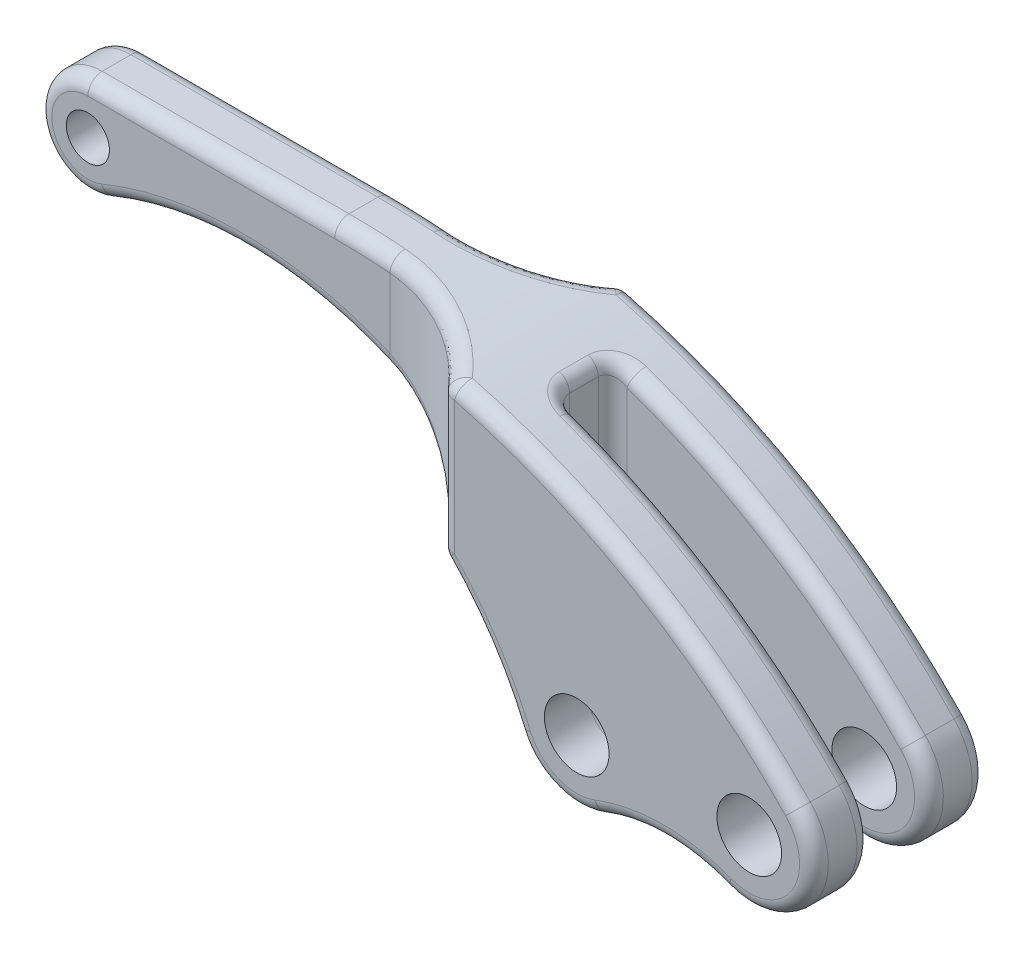
SolidWorks part; units mm, degrees
ref_plane "Front Plane" through (0, 0, 0) normal (0, 0, 1) x (1, 0, 0)
ref_plane "Top Plane" through (0, 0, 0) normal (0, 1, 0) x (1, 0, 0)
ref_plane "Right Plane" through (0, 0, 0) normal (1, 0, 0) x (0, 0, -1)
sketch "Sketch1" plane through (0, 0, 0) normal (0, 0, 1) x (1, 0, 0)
  line L0 (76, -30) -> (100, -30) construction
  line L1 (0, 7) -> (34.3342, 7)
  circle A0 centre (0, 0) radius 3
  arc A1 (0, 7) -> (2.6487, -6.4796) centre (0, 0) ccw
  arc A2 (96.7273, -38.3839) -> (106.4944, -23.7692) centre (100, -30) ccw
  arc A3 (67.6968, -33.4722) -> (79.2727, -38.3839) centre (76, -30) ccw
  arc A4 (79.2727, -38.3839) -> (96.7273, -38.3839) centre (88, -60.7409) cw
  arc A5 (2.6487, -6.4796) -> (67.6968, -33.4722) centre (21.5676, -52.7621) cw
  arc A6 (34.3342, 7) -> (106.4944, -23.7692) centre (34.3342, -93) cw
  circle A7 centre (76, -30) radius 4.5
  circle A8 centre (100, -30) radius 4.5
  dimension "D1" = 6
  dimension "D2" = 14
  dimension "D3" = 18
  dimension "D6" = 18
  dimension "D8" = 24
  dimension "D9" = 50
  dimension "D10" = 100
  dimension "D11" = 9
  dimension "D12" = 9
  dimension "D4" = 100
  dimension "D5" = 30
  dimension "D7" = 24
extrude "Boss-Extrude1" add sketch "Sketch1" along normal mid plane 24
sketch "Sketch2" plane through (0, 0, 0) normal (0, 1, 0) x (1, 0, 0)
  line L0 (-7, 4) -> (-7, -4)
  line L1 (-7, 12) -> (-7, -12) construction
  line L2 (-7, 0) -> (108.7222, 0) construction
  line L3 (-7, -12) -> (58, -12)
  line L4 (-7, -12) -> (2.6487, -12) construction
  line L5 (34.3342, -12) -> (106.4944, -12) construction
  line L6 (-7, -4) -> (42, -4)
  line L7 (-7, -4) -> (-7, -12)
  line L8 (-7, 12) -> (58, 12)
  line L9 (-7, 4) -> (-7, 12)
  line L10 (-7, 4) -> (42, 4)
  line L11 (65, -12) -> (100, -12)
  line L12 (109, 4) -> (65, 4)
  line L13 (109, -12) -> (109, 12) construction
  line L14 (65, 4) -> (65, -4)
  line L15 (65, -4) -> (109, -4)
  line L16 (109, -4) -> (109, 4)
  line L17 (65, -12) -> (65, 17.4758) construction
  arc A0 (42, -4) -> (58, -12) centre (42, -24) cw
  arc A1 (42, 4) -> (58, 12) centre (42, 24) ccw
  point P7 (-7, 0)
  dimension "D3" = 20
  dimension "D1" = 8
  dimension "D2" = 65
  dimension "D4" = 100
  dimension "D5" = 8
  dimension "D6" = 35
extrude "Cut-Extrude1" cut sketch "Sketch2" against normal mid plane 91 contours L10 A1 L8 L9 | A0 L6 L7 L3 | L12 L14 L15 L16
fillet "Fillet3" radius 2 40 edges at (72.4846, -38.2851, 12) (84.2407, -6.3435, 12) (107.4828, -35.0008, 12) (88, -36.7409, 12) (72.4846, -38.2851, -12) (84.2407, -6.3435, -12) (107.4828, -35.0008, -12) (88, -36.7409, -12) (53.068, 5.2295, 7.3417) (49.0899, -11.0186, 5.2988) (53.068, 5.2295, -7.3417) (49.0899, -11.0186, -5.2988) (38.1699, 6.9264, 4) (17.1671, 7, 4) (-6.8687, -1.3496, 4) (22.3908, -2.7689, 4) (38.1699, 6.9264, -4) (17.1671, 7, -4) (-6.8687, -1.3496, -4) (22.3908, -2.7689, -4) (65, 2.182, 0) (87.3593, -8.216, 4) (107.4828, -35.0008, 4) (88, -36.7409, 4) (72.4846, -38.2851, 4) (80.5, -30, 4) (87.3593, -8.216, -4) (107.4828, -35.0008, -4) (88, -36.7409, -4) (72.4846, -38.2851, -4) (71.5, -30, -4) (58, -7.1792, -12) (58, -7.1792, 12) (65, -12.9043, -4) (65, -12.9043, 4) (65, -27.9906, 0) (63.5201, -25.5594, 12) (63.5201, -25.5594, -12) (66.4322, -30.6902, 4) (66.4322, -30.6902, -4)
